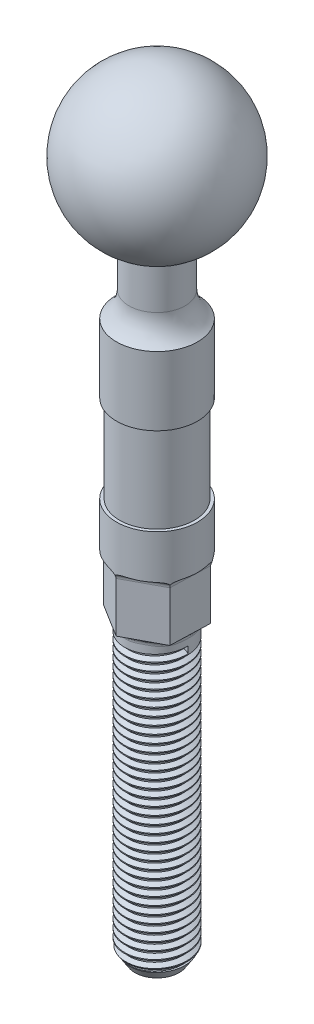
SolidWorks part; units mm, degrees
ref_plane "Front Plane" through (0, 0, 0) normal (0, 0, 1) x (1, 0, 0)
ref_plane "Top Plane" through (0, 0, 0) normal (0, 1, 0) x (1, 0, 0)
ref_plane "Right Plane" through (0, 0, 0) normal (1, 0, 0) x (0, 0, -1)
sketch "Sketch1" plane through (0, 0, 0) normal (0, 0, 1) x (1, 0, 0)
  line L0 (0, 0) -> (0, 25)
  arc A0 (0, 25) -> (0, 0) centre (0, 12.5) cw
  dimension "D1" = 25
revolve "Revolve1" add sketch "Sketch1" angle 360 about L0 region at (5.3052, 12.5, 0) other way angle 360
sketch "Sketch2" plane through (0, 0, 0) normal (0, 1, 0) x (1, 0, 0)
  circle A0 centre (0, 0) radius 4.5
  dimension "D1" = 9
extrude "Boss-Extrude1" add sketch "Sketch2" against normal blind 10 and the other way blind 10
sketch "Sketch3" plane through (0, -10, 0) normal (0, -1, 0) x (1, 0, 0)
  circle A0 centre (0, 0) radius 6.5
  dimension "D1" = 13
extrude "Boss-Extrude2" add sketch "Sketch3" along normal blind 32
fillet "Fillet1" radius 5 1 edges at (0, -10, 4.5)
sketch "Sketch4" plane through (0, 0, 0) normal (0, 0, 1) x (1, 0, 0)
  line L0 (6.5, -42) -> (6.5, -10) construction
  line L1 (6.5, -21) -> (6, -21)
  line L2 (6.5, -21) -> (6.5, -35)
  line L3 (6.5, -35) -> (6, -35)
  line L4 (6, -21) -> (6, -35)
  line L5 (6.5, -10) -> (-6.5, -10) construction
  dimension "D1" = 0.5
  dimension "D2" = 14
  dimension "D3" = 11
revolve "Cut-Revolve1" cut sketch "Sketch4" angle 360 about axis through (0, -42, 0) along (0, 1, 0)
sketch "Sketch5" plane through (0, -42, 0) normal (0, -1, 0) x (1, 0, 0)
  line L1 (5.5996, -2.9964) -> (5.3947, 3.3512)
  line L2 (5.3947, 3.3512) -> (-0.2048, 6.3475)
  line L3 (-0.2048, 6.3475) -> (-5.5996, 2.9964)
  line L4 (-5.5996, 2.9964) -> (-5.3947, -3.3512)
  line L5 (-5.3947, -3.3512) -> (0.2048, -6.3475)
  line L6 (0.2048, -6.3475) -> (5.5996, -2.9964)
  circle A0 centre (0, 0) radius 5.5 construction
extrude "Boss-Extrude3" add sketch "Sketch5" along normal blind 9
fillet "Fillet2" radius 1 6 edges at (2.5949, -42, 4.8494) (5.4971, -42, 0.1774) (2.9022, -42, -4.672) (-2.5949, -42, -4.8494) (-5.4971, -42, -0.1774) (-2.9022, -42, 4.672)
sketch "Sketch6" plane through (0, -51, 0) normal (0, -1, 0) x (1, 0, 0)
  circle A0 centre (0, 0) radius 5
  dimension "D1" = 10
extrude "Boss-Extrude4" add sketch "Sketch6" along normal blind 48
fillet "Fillet3" radius 1 1 edges at (0, -51, -5)
thread "Thread1" pitch 1.25 method cut profile "Thread Profile1" start angle 0, offset 0, length 45, pitch 1.25, diameter 10
ref_plane "Plane1" through (5, -99, 0) normal (0, 0, 1) x (1, 0, 0)
sketch "Thread Profile1" plane through (5, -99, 0) normal (0, 0, 1) x (1, 0, 0)
  line L0 (0, 0) -> (0, 1.25) construction
  line L11 (0, 0) -> (0, 1.0937)
  line L12 (0, 1.0937) -> (-0.6766, 0.7031)
  line L13 (-0.6766, 0.7031) -> (-0.6766, 0.3906)
  line L15 (-0.6766, 0.3906) -> (0, 0)
  line L17 (-0.6766, 0.5469) -> (0, 0.5469) construction
  point P2 (0, 0)
  dimension "Pitch" = 1.25
  dimension "Profile_Angle" = 60
  dimension "Profile_Land" = 0.3125
  dimension "Profile_Height" = 0.6766
sketch "Sketch11" plane through (0, 0, 0) normal (0, 0, 1) x (1, 0, 0)
  line L0 (2.8916, -100.025) -> (7.4892, -92.8533)
  line L1 (7.4892, -92.8533) -> (7.0429, -102.5694)
  line L2 (7.0429, -102.5694) -> (2.8916, -100.025)
revolve "Cut-Revolve2" cut sketch "Sketch11" angle 360 about axis through (0, -99, 0) along (0, 1, 0)
